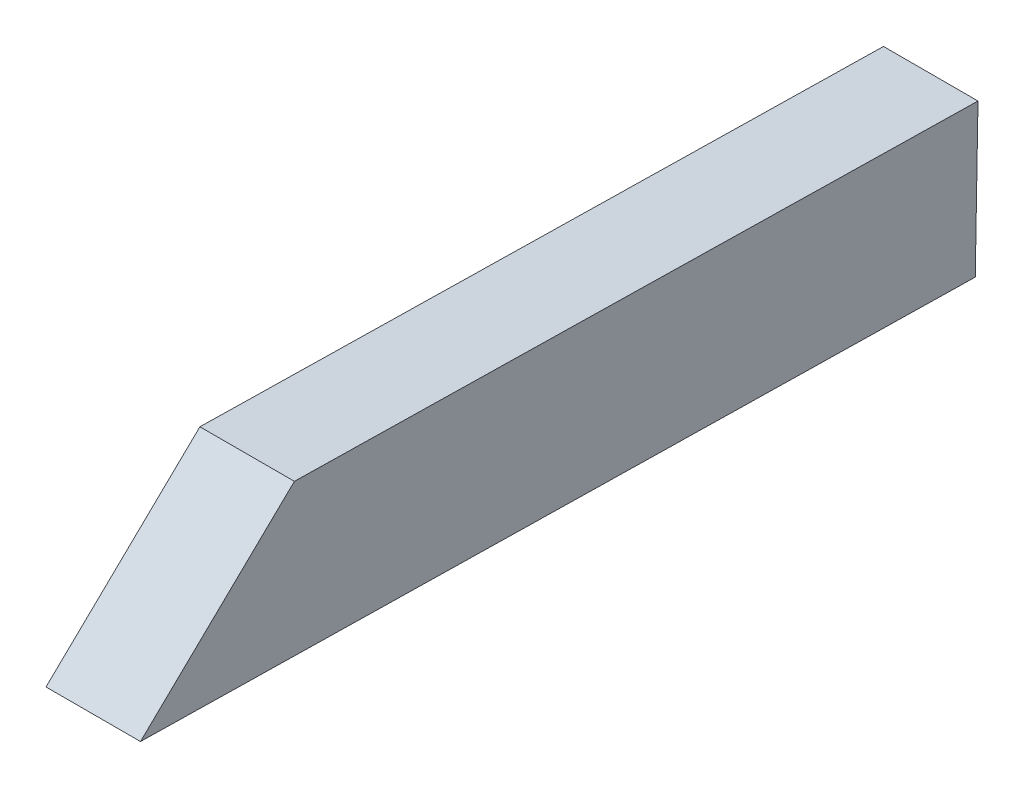
SolidWorks part; units mm, degrees
ref_plane "Front Plane" through (0, 0, 0) normal (0, 0, 1) x (1, 0, 0)
ref_plane "Top Plane" through (0, 0, 0) normal (0, 1, 0) x (1, 0, 0)
ref_plane "Right Plane" through (0, 0, 0) normal (1, 0, 0) x (0, 0, -1)
sketch "Sketch2" plane through (0, 1065.8103, -19.3901) normal (0, 0.9998, -0.0182) x (1, 0, 0)
  line L0 (695.0072, -1305.2676) -> (669.6072, -1305.2676) construction
  line L1 (669.6072, -1277.2123) -> (672.7822, -1277.2123)
  line L2 (669.6072, -1277.2123) -> (669.6072, -1305.2676)
  line L3 (669.6072, -1305.2676) -> (672.7822, -1305.2676)
  line L4 (672.7822, -1277.2123) -> (672.7822, -1305.2676)
  dimension "D1" = 3.175
extrude "Boss-Extrude1" add sketch "Sketch2" along normal blind 5.08
chamfer "Chamfer1" distance 5.08 angle 45 1 edges at (671.1947, 1094.632, 1285.5691)
